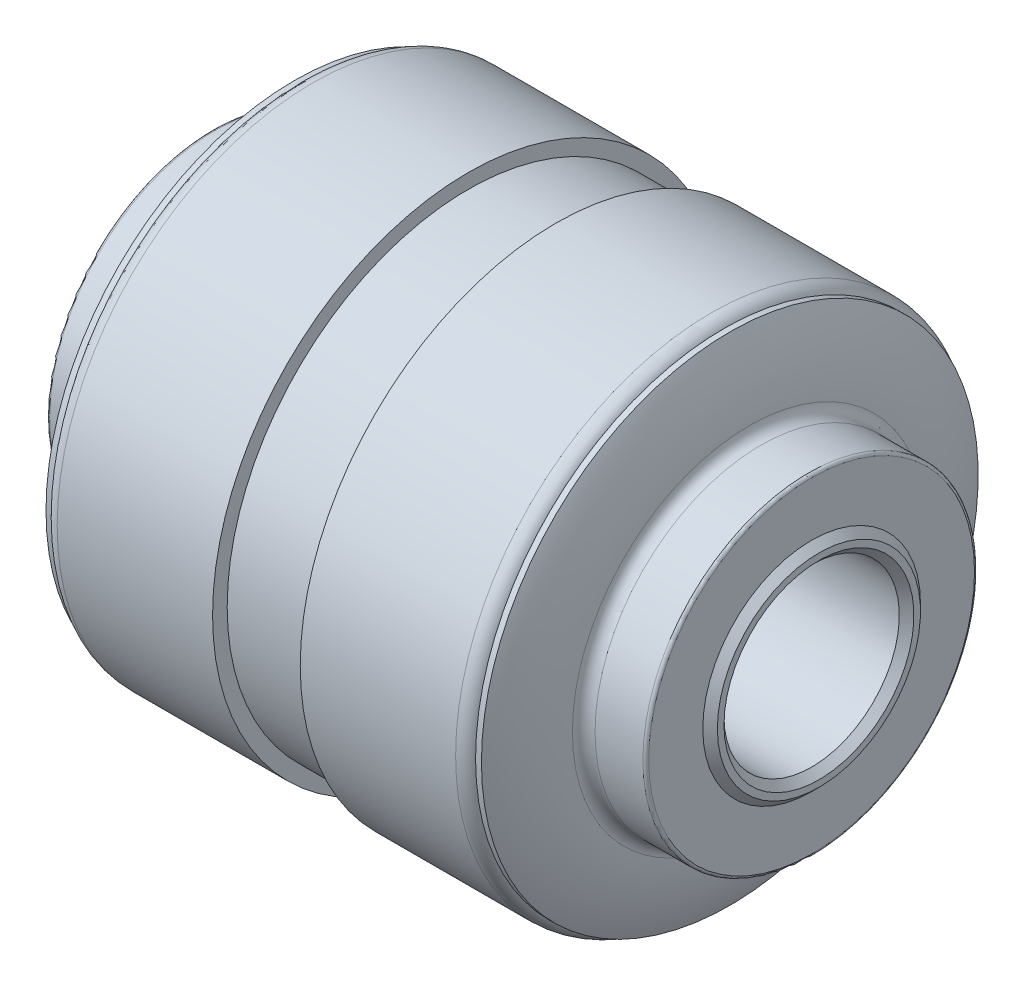
SolidWorks part; units mm, degrees
ref_plane "Front Plane" through (0, 0, 0) normal (0, 0, 1) x (1, 0, 0)
ref_plane "Top Plane" through (0, 0, 0) normal (0, 1, 0) x (1, 0, 0)
ref_plane "Right Plane" through (0, 0, 0) normal (1, 0, 0) x (0, 0, -1)
ref_axis "Axis_X" through (-88.99, 0, 0) along (1, 0, 0)
ref_axis "Axis_Y" through (0, 55, 0) along (0, -1, 0)
ref_axis "Axis_Z" through (0, 0, -88.99) along (0, 0, 1)
sketch "Sketch1" plane through (0, 0, 0) normal (0, 0, 1) x (1, 0, 0)
  line L0 (0, 6) -> (21, 6)
  line L1 (21, 6) -> (21, 7.45)
  line L2 (21, 7.45) -> (20.5, 7.45)
  line L3 (20.5, 7.45) -> (20.5, 11.35)
  line L4 (20.5, 11.35) -> (16.25, 11.35)
  line L5 (16.25, 11.35) -> (16.25, 17)
  line L6 (14.5, 17.5) -> (3, 17.5)
  line L7 (3, 17.5) -> (3, 16.5)
  line L8 (3, 16.5) -> (0, 16.5)
  line L9 (0, 16.5) -> (0, 6)
  line L10 (0, 0) -> (0, 16.5) construction
  line L11 (0, 0) -> (21, 0) construction
  line L12 (14.5, 17.5) -> (14.5, 17)
  line L13 (14.5, 17) -> (16.25, 17)
  dimension "FIX_1" = 6
  dimension "FIX_2" = 33
  dimension "FIX_3" = 35
  dimension "FIX_4" = 32.5
  dimension "FIX_5" = 4.25
  dimension "FIX_6" = 22.7
  dimension "FIX_7" = 12
  dimension "FIX_8" = 14.9
  dimension "FIX_9" = 0.5
  dimension "FIX_10" = 0.5
  dimension "FIX_11" = 6
revolve "Revolve1" add sketch "Sketch1" angle 360 about axis through (-88.99, 0, 0) along (1, 0, 0)
sketch "Sketch2" plane through (0, 0, 0) normal (0, 0, 1) x (1, 0, 0)
  line L0 (14.6324, 17.5) -> (16.25, 17.5)
  line L1 (16.25, 17.5) -> (16.25, 11.35)
  line L2 (14.5, 17.5) -> (3, 17.5) construction
  line L3 (16.25, -17.5) -> (16.25, 17.5) construction
  line L4 (20.5, 11.35) -> (16.25, 11.35) construction
  arc A0 (16.25, 11.35) -> (14.6324, 17.5) centre (3.75, 11.35) ccw
  dimension "FIX_13" = 12.5
revolve "Cut-Revolve1" cut sketch "Sketch2" angle 360 about axis through (-88.99, 0, 0) along (1, 0, 0)
mirror "Mirror1" about plane through (0, 0, 0) normal (1, 0, 0) of "Cut-Revolve1", "Revolve1"
chamfer "Chamfer1" distance 0.5 angle 45 4 edges at (21, 0, 6) (21, 0, 7.45) (-21, 0, 6) (-21, 0, 7.45)
fillet "Fillet1" radius 0.2 2 edges at (20.5, 0, 11.35) (-20.5, 0, 11.35)
fillet "Fillet2" radius 0.8 2 edges at (-16.25, 0, 11.35) (16.25, 0, 11.35)
fillet "Fillet3" radius 1 2 edges at (14.5, 0, 17.5) (-14.5, 0, 17.5)
equation "\"Factor\"= 1.082532"
